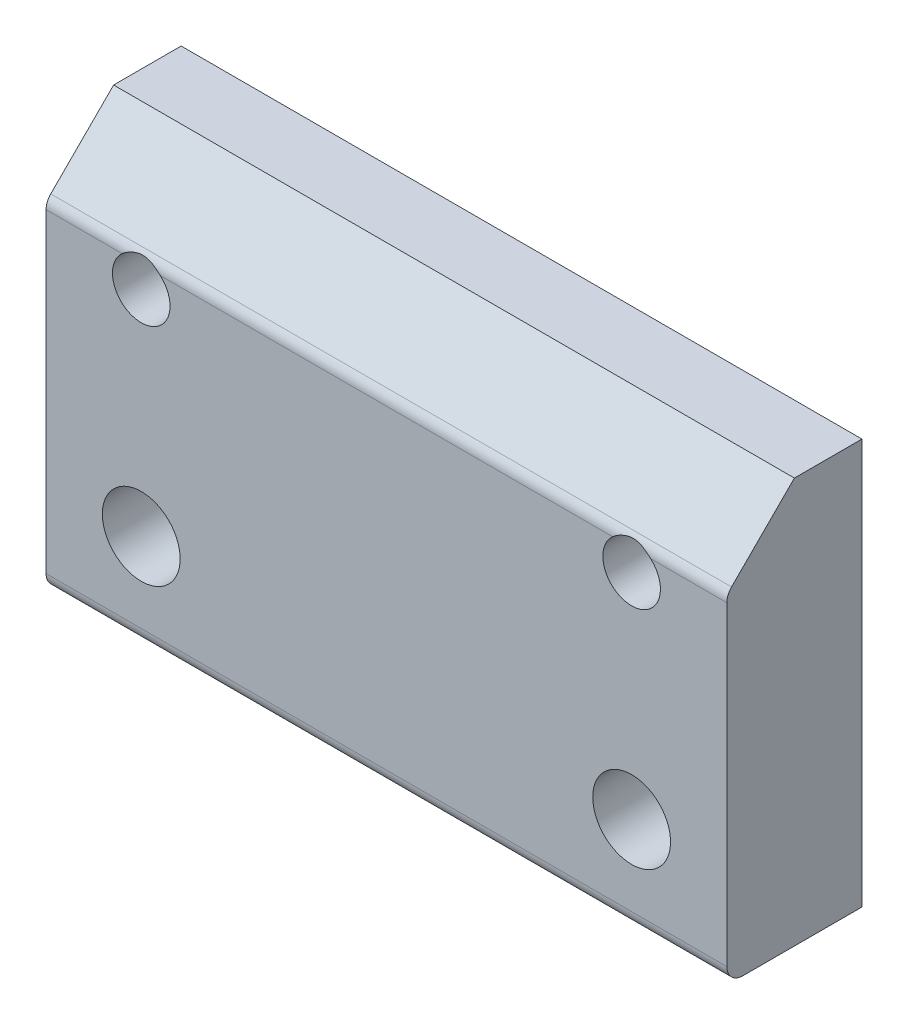
SolidWorks part; units mm, degrees
note: '?' marks a value the reader was unsure of.
material "6061-T6 (SS)"
ref_plane "Front" through (0, 0, 0) normal (0, 0, 1) x (1, 0, 0)
ref_plane "Top" through (0, 0, 0) normal (0, 1, 0) x (1, 0, 0)
ref_plane "Right" through (0, 0, 0) normal (1, 0, 0) x (0, 0, -1)
ref_axis "side-side" through (80.9, 0, 0) along (-1, 0, 0)?
ref_axis "up-down" through (0, 50, 0) along (0, -1, 0)?
ref_axis "front-back" through (0, 0, -80.9) along (0, 0, 1)?
sketch "Sketch1" plane through (0, 0, 0) normal (1, 0, 0) x (0, 0, -1)
  line L0 (0, 6.35) -> (3.175, 9.525)
  line L1 (3.175, 9.525) -> (6.35, 9.525)
  line L2 (0, 6.35) -> (0, -9.525)
  line L3 (0, -9.525) -> (6.35, -9.525)
  line L4 (6.35, 9.525) -> (6.35, -9.525)
  point P0 (6.35, 0)
  dimension "D1" = 6.35
  dimension "D2" = 19.05
  dimension "D3" = 45
  dimension "D4" = 3.175
extrude "Boss-Extrude1" add sketch "Sketch1" along normal mid plane 32
hole_wizard "#6-32 Tapped Hole1" positions "Sketch3" profile "Sketch5" tap size "#6-32" standard "ANSI Inch"
sketch "Sketch3" plane through (0, 0, -6.35) normal (0, 0, -1) x (-1, 0, 0)
  line L0 (-9.525, 9.525) -> (-9.525, -9.525) construction
  line L1 (-16, 9.525) -> (16, 9.525) construction
  line L2 (-16, -9.525) -> (16, -9.525) construction
  line L3 (0, 0) -> (0, 16.0303) construction
  point P7 (-11.525, 5.025)
  point P11 (11.525, 5.025)
  dimension "D1" = 9.525
  dimension "D2" = 4.5
  dimension "D4" = 2
  dimension "D5" = 23.05
sketch "Sketch5" plane through (-11.525, 5.025, -6.35) normal (1, 0, 0) x (0, 1, 0)
  line L0 (0, 0) -> (0, 10.2107)
  line L1 (0, 10.2107) -> (1.3525, 9.398)
  line L2 (1.3525, 9.398) -> (1.3525, 0)
  line L5 (1.3525, 0) -> (0, 0)
  line L10 (0, 10.2107) -> (-1.3526, 9.398) construction
  line L11 (0, -6.35) -> (0, 107.95) construction
  dimension "Tap Drill Dia." = 2.7051
  dimension "Tap Drill Depth" = 9.398
  dimension "Drill Angle" = 118
hole_wizard "#6 Clearance Hole1" [suppressed] positions "Sketch6" profile "Sketch7" hole size "#6" standard "ANSI Inch"
sketch "Sketch6" plane through (0, -9.525, 0) normal (0, -1, 0) x (-1, 0, 0)
  line L0 (-21, 0) -> (21, 0) construction
  line L2 (0, 0) -> (0, 28.1383) construction
  point P0 (-15.525, 0)
  point P7 (15.525, 0)
  dimension "D1" = 31.05
sketch "Sketch7" plane through (15.525, -9.525, 0) normal (1, 0, 0) x (0, 0, -1)
  line L0 (0, 0) -> (0, 19.05)
  line L1 (0, 19.05) -> (1.8288, 19.05)
  line L2 (1.8288, 19.05) -> (1.8288, 0)
  line L5 (1.8288, 0) -> (0, 0)
  line L11 (0, -6.35) -> (0, 107.95) construction
  dimension "Thru Hole Dia." = 3.6576
  dimension "Thru Hole Depth" = 19.05
fillet "Fillet1" radius 0.75 2 edges at (0, -9.525, 0) (0, 6.35, 0)
hole_wizard "#6 Clearance Hole2" positions "Sketch8" profile "Sketch9" hole size "#6" standard "ANSI Inch" end condition through all
sketch "Sketch8" plane through (0, 0, -6.35) normal (0, 0, -1) x (-1, 0, 0)
  line L0 (0, 0) -> (0, -17.7087) construction
  line L1 (-16, -9.525) -> (16, -9.525) construction
  point P3 (11.525, -5.025)
  point P5 (-11.525, -5.025)
  dimension "D1" = 4.5
sketch "Sketch9" plane through (11.525, -5.025, -6.35) normal (1, 0, 0) x (0, 1, 0)
  line L0 (0, 0) -> (0, 6.35)
  line L1 (0, 6.35) -> (1.8288, 6.35)
  line L2 (1.8288, 6.35) -> (1.8288, 0)
  line L5 (1.8288, 0) -> (0, 0)
  line L11 (0, -6.35) -> (0, 107.95) construction
  dimension "Thru Hole Dia." = 3.6576
  dimension "Thru Hole Depth" = 6.35
